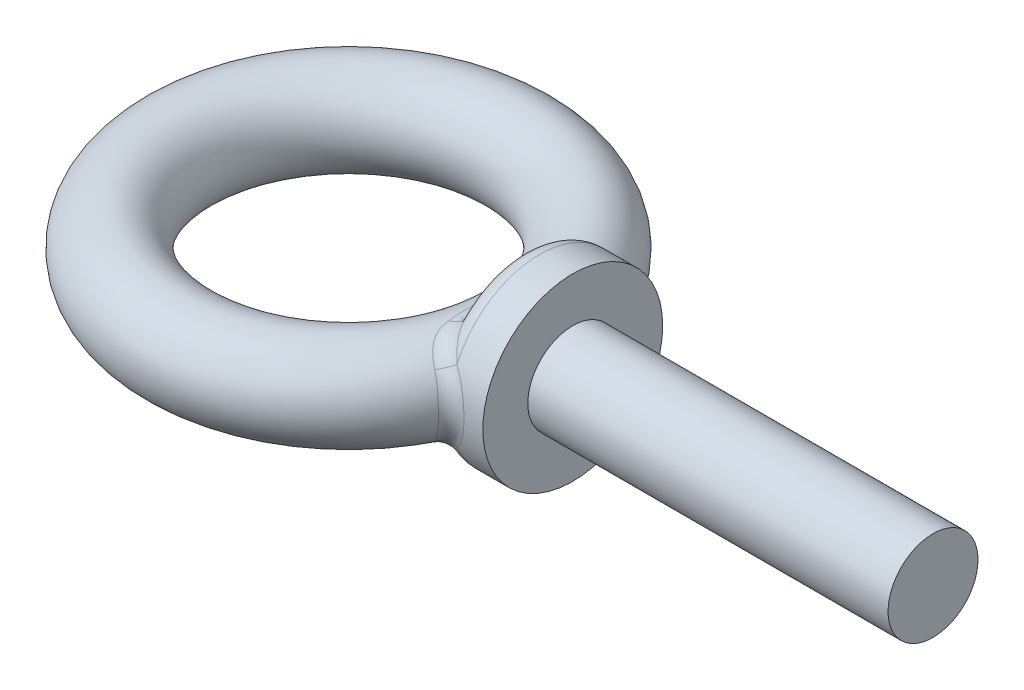
SolidWorks part; units mm, degrees
ref_plane "Front Plane" through (0, 0, 0) normal (0, 0, 1) x (1, 0, 0)
ref_plane "Top Plane" through (0, 0, 0) normal (0, 1, 0) x (1, 0, 0)
ref_plane "Right Plane" through (0, 0, 0) normal (1, 0, 0) x (0, 0, -1)
sketch "layout" plane through (0, 0, 0) normal (0, 1, 0) x (1, 0, 0)
  line L0 (0, 0) -> (41.275, 0) construction
  line L1 (-8.763, 0) -> (-15.113, 0) construction
  circle A0 centre (0, 0) radius 15.113 construction
  circle A1 centre (0, 0) radius 8.763 construction
  dimension "D1" = 30.226
sketch "Sketch2" plane through (0, 0, 0) normal (0, 0, 1) x (1, 0, 0)
  line L3 (0, 0) -> (0, 6.6909) construction
  line L4 (15.113, 0) -> (-15.113, 0) construction
  circle A0 centre (-11.938, 0) radius 3.175
  point P4 (-15.113, 0)
  dimension "D1" = 6.35
revolve "Revolve1" add sketch "Sketch2" angle 360 about L3
sketch "Sketch3" plane through (0, 0, 0) normal (0, 1, 0) x (1, 0, 0)
  line L0 (13.7142, 0) -> (13.7142, 6.35) construction
  line L1 (15.8372, 6.35) -> (15.8372, 3.175)
  line L2 (15.8372, 3.175) -> (41.275, 3.175)
  line L3 (41.275, 3.175) -> (41.275, 0)
  line L4 (0, 0) -> (59.9404, 0) construction
  line L5 (13.7142, 6.35) -> (15.8372, 6.35)
  line L6 (13.7142, 0) -> (8.763, 0) construction
  line L7 (0, 0) -> (41.275, 0) construction
  line L8 (11.2386, 0) -> (11.2386, -2.9252) construction
  line L9 (41.275, 0) -> (11.2386, 0)
  line L10 (14.7757, 3.175) -> (13.7142, 3.175) construction
  line L11 (12.9715, 17.6146) -> (15.0945, 17.6146) construction
  line L12 (15.0945, 17.6146) -> (12.9715, 18.6761) construction
  line L13 (12.6527, 6.35) -> (13.7142, 6.35)
  line L14 (12.9715, 18.1453) -> (14.033, 18.1453) construction
  line L15 (12.9715, 18.6761) -> (12.9715, 17.6146) construction
  line L16 (14.7757, 3.175) -> (15.8372, 3.175) construction
  circle A1 centre (0, 0) radius 15.113 construction
  arc A2 (12.6527, 6.35) -> (11.2386, 0) centre (26.2027, 0) ccw
  circle A4 centre (0, 0) radius 8.763 construction
  dimension "D2" = 6.35
  dimension "K" = 12.7
revolve "Revolve2" add sketch "Sketch3" angle 360 about L9
cosmetic thread "Cosmetic Thread1" [suppressed] parameters "D1"=19.05, "D2"=4.7625
fillet "Fillet1" radius 1.27 6 edges at (13.6966, 0.3584, 6.3399) (13.6966, -0.3584, -6.3399) (11.5928, -3.1584, -0.7057) (11.5928, 3.1584, 0.7057) (12.6527, -6.35, 0) (12.6527, 6.35, 0)
sketch "Sketch4" plane through (0, 0, 0) normal (0, 1, 0) x (1, 0, 0)
  line L0 (41.275, 2.3813) -> (41.7333, 3.175)
  line L1 (41.7333, 3.175) -> (41.7333, 4.0915)
  line L2 (41.7333, 4.0915) -> (40.8167, 4.0915)
  line L3 (40.8167, 4.0915) -> (40.8167, 3.175)
  line L4 (40.8167, 3.175) -> (41.275, 2.3813)
  line L5 (0, 0) -> (44.568, 0) construction
  line L6 (41.275, -3.175) -> (41.275, 3.175) construction
  dimension "D2" = 6.35
  dimension "D1" = 4.7625
revolve "Cut-Revolve1" [suppressed] cut sketch "Sketch4" angle 360 about L5
pattern_linear "LPattern1" [suppressed] count 15 along (-1, 0, 0) of bodies 106
equation "\"D1@Sketch2\" = \"DIA@layout\""
equation "\"D2@Sketch3\" = \"DIA@layout\""
equation "\"D1@Fillet1\" = \"DIA@layout\" / 5"
equation "\"D1@Sketch4\" = \"D2@Cosmetic Thread1\""
equation "\"D2@Sketch4\" = \"DIA@layout\""
equation "\"D1@LPattern1\" = \"D1@Cosmetic Thread1\" / \"P@LPattern1\""
